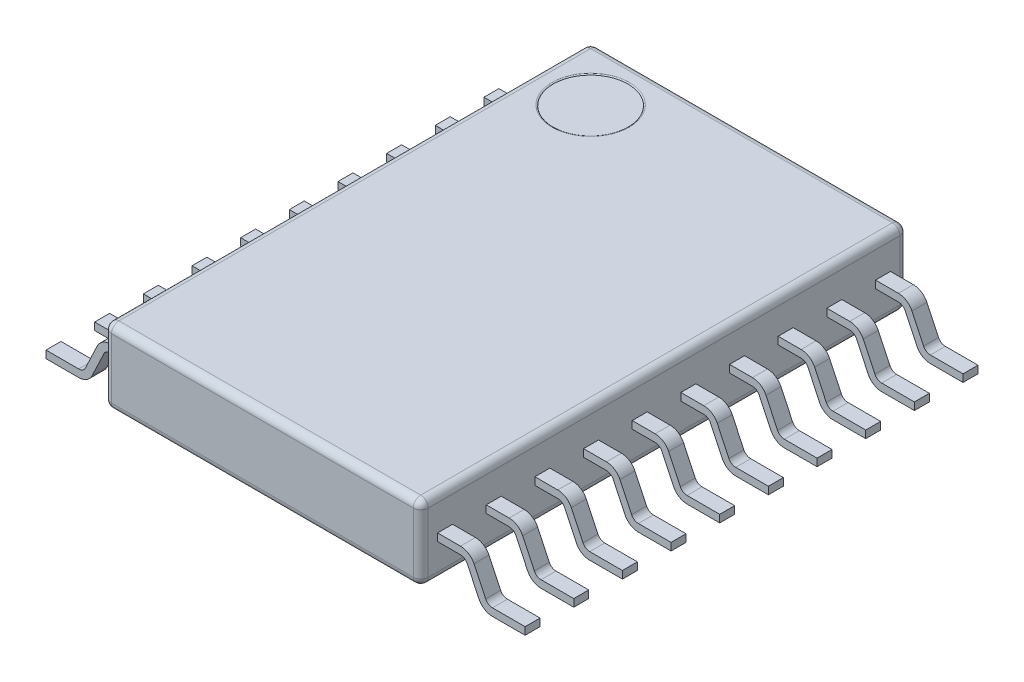
SolidWorks part; units mm, degrees
ref_plane "Front Plane" through (0, 0, 0) normal (0, 0, 1) x (1, 0, 0)
ref_plane "Top Plane" through (0, 0, 0) normal (0, 1, 0) x (1, 0, 0)
ref_plane "Right Plane" through (0, 0, 0) normal (1, 0, 0) x (0, 0, -1)
sketch "Sketch1" plane through (0, 0, 0) normal (0, 0, 1) x (1, 0, 0)
  line L0 (0, 0) -> (-0.4367, 0)
  line L3 (-0.6175, 0.1144) -> (-0.7729, 0.4428)
  line L8 (0, 0.1) -> (-0.4367, 0.1)
  line L12 (-5.7825, 0.1144) -> (-5.6271, 0.4428)
  line L13 (-6.4, 0) -> (-5.9633, 0)
  line L14 (-0.8633, 0.5) -> (-5.5367, 0.5)
  line L15 (-0.5271, 0.1572) -> (-0.6825, 0.4856)
  line L16 (-0.8633, 0.6) -> (-5.5367, 0.6)
  line L17 (-5.8729, 0.1572) -> (-5.7175, 0.4856)
  line L18 (-6.4, 0.1) -> (-5.9633, 0.1)
  line L19 (0, 0.1) -> (0, 0)
  line L20 (-6.4, 0.1) -> (-6.4, 0)
  arc A0 (-0.4367, 0) -> (-0.6175, 0.1144) centre (-0.4367, 0.2) cw
  arc A1 (-0.8633, 0.5) -> (-0.7729, 0.4428) centre (-0.8633, 0.4) cw
  arc A2 (-5.5367, 0.5) -> (-5.6271, 0.4428) centre (-5.5367, 0.4) ccw
  arc A3 (-5.9633, 0) -> (-5.7825, 0.1144) centre (-5.9633, 0.2) ccw
  arc A4 (-0.4367, 0.1) -> (-0.5271, 0.1572) centre (-0.4367, 0.2) cw
  arc A5 (-0.8633, 0.6) -> (-0.6825, 0.4856) centre (-0.8633, 0.4) cw
  arc A6 (-5.5367, 0.6) -> (-5.7175, 0.4856) centre (-5.5367, 0.4) ccw
  arc A7 (-5.9633, 0.1) -> (-5.8729, 0.1572) centre (-5.9633, 0.2) ccw
  dimension "D1" = 0.2
  dimension "D6" = 5.5367
  dimension "D2" = 0.1
  dimension "D3" = 0.4367
  dimension "D4" = 0.5271
  dimension "D5" = 0.6825
extrude "Boss-Extrude2" add sketch "Sketch1" against normal blind 0.2 contours L16 A6 L17 A7 L18 L20 L13 A3 L12 A2 L14 A1 L3 A0 L0 L19 L8 A4 L15 A5
ref_plane "Plane1" through (0, 0.05, 0) normal (0, 1, 0) x (1, 0, 0)
sketch "Sketch2" plane through (0, 0.05, 0) normal (0, 1, 0) x (1, 0, 0)
  line L0 (0, 0.1) -> (0, -0.225)
  line L1 (0, 0.2) -> (0, 0) construction
  line L3 (-6.4, 0.1) -> (-6.4, -0.225)
  line L4 (-6.4, 0.2) -> (-6.4, 0) construction
  line L7 (-5.4, -0.225) -> (-1.1691, -0.225)
  line L8 (-5.4, -0.225) -> (-5.4, 6.275)
  line L9 (-5.4, 6.275) -> (-1.1691, 6.275)
  line L10 (-1.1691, -0.225) -> (-1.1691, 6.275)
  dimension "D1" = 1.1691
  dimension "D2" = 5.4
  dimension "D3" = 6.275
  dimension "D4" = 0.225
extrude "Boss-Extrude3" add sketch "Sketch2" along normal blind 1 contours L7 L10 L9 L8 region at (-3.2846, 0.05, -3.025)
pattern_linear "LPattern2" count 10 spacing 0.65 along (0, 0, -1) of "Boss-Extrude2"
fillet "Fillet1" radius 0.1 8 edges at (-1.1691, 0.05, -3.025) (-3.2846, 0.05, -6.275) (-5.4, 0.05, -3.025) (-3.2846, 0.05, 0.225) (-3.2846, 1.05, -6.275) (-1.1691, 1.05, -3.025) (-3.2846, 1.05, 0.225) (-5.4, 1.05, -3.025)
fillet "Fillet2" radius 0.1 12 edges at (-5.3707, 1.0207, -6.2457) (-5.3707, 0.0793, -6.2457) (-1.1984, 1.0207, -6.2457) (-1.1984, 0.0793, -6.2457) (-5.3707, 1.0207, 0.1957) (-5.3707, 0.0793, 0.1957) (-1.1984, 1.0207, 0.1957) (-1.1984, 0.0793, 0.1957) (-5.4, 0.55, -6.275) (-1.1691, 0.55, -6.275) (-5.4, 0.55, 0.225) (-1.1691, 0.55, 0.225)
sketch "Sketch3" plane through (0, 1.05, 0) normal (0, 1, 0) x (1, 0, 0)
  line L0 (-1.2691, -0.125) -> (-1.2691, 6.175) construction
  circle A0 centre (-4.65, 5.525) radius 0.5
  point P7 (0, 0)
  dimension "D1" = 1
  dimension "D2" = 3.3809
  dimension "D3" = 0.65
extrude "Cut-Extrude1" cut sketch "Sketch3" against normal blind 0.01 contours A0
fillet "Fillet3" radius 0.02 1 edges at (-4.65, 1.05, -5.025)
